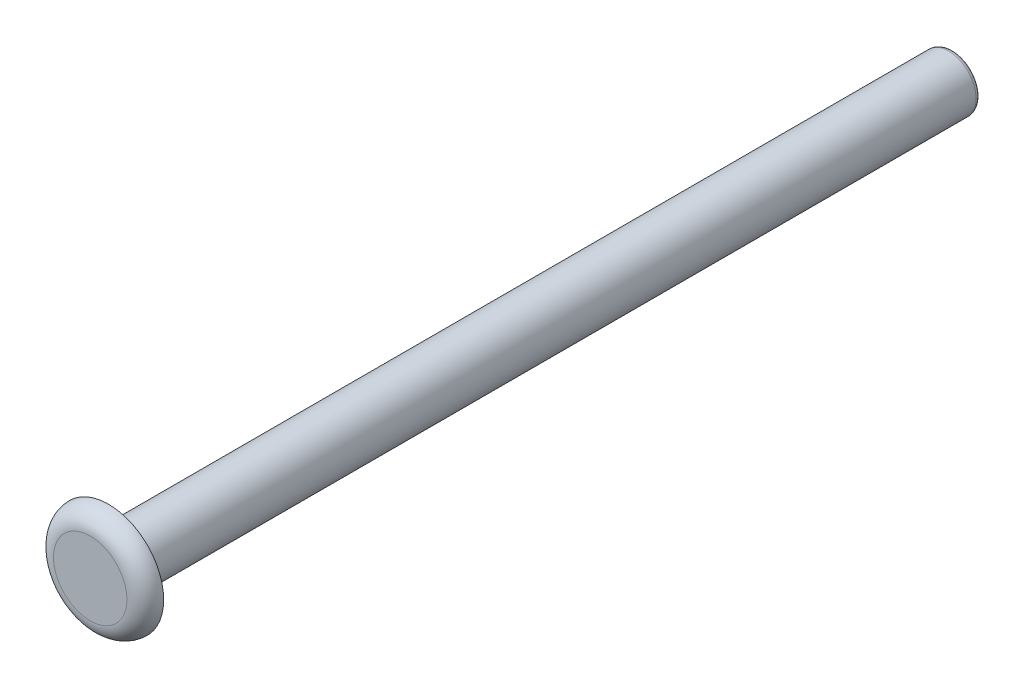
SolidWorks part; units mm, degrees
ref_plane "Front Plane" through (0, 0, 0) normal (0, 0, 1) x (1, 0, 0)
ref_plane "Top Plane" through (0, 0, 0) normal (0, 1, 0) x (1, 0, 0)
ref_plane "Right Plane" through (0, 0, 0) normal (1, 0, 0) x (0, 0, -1)
sketch "Esquisse1" plane through (0, 0, 0) normal (0, 0, 1) x (1, 0, 0)
  circle A0 centre (-28.0683, 21.8847) radius 1.5
  dimension "D1" = 3
extrude "Boss.-Extru.1" add sketch "Esquisse1" along normal blind 46
sketch "Esquisse2" plane through (0, 0, 46) normal (0, 0, 1) x (1, 0, 0)
  circle A0 centre (-28.0683, 21.8847) radius 3
  dimension "D1" = 6
extrude "Boss.-Extru.2" add sketch "Esquisse2" along normal blind 1
fillet "Congé1" radius 1 1 edges at (-25.0683, 21.8847, 47)
fillet "Congé2" radius 0.25 1 edges at (-26.5683, 21.8847, 0)
